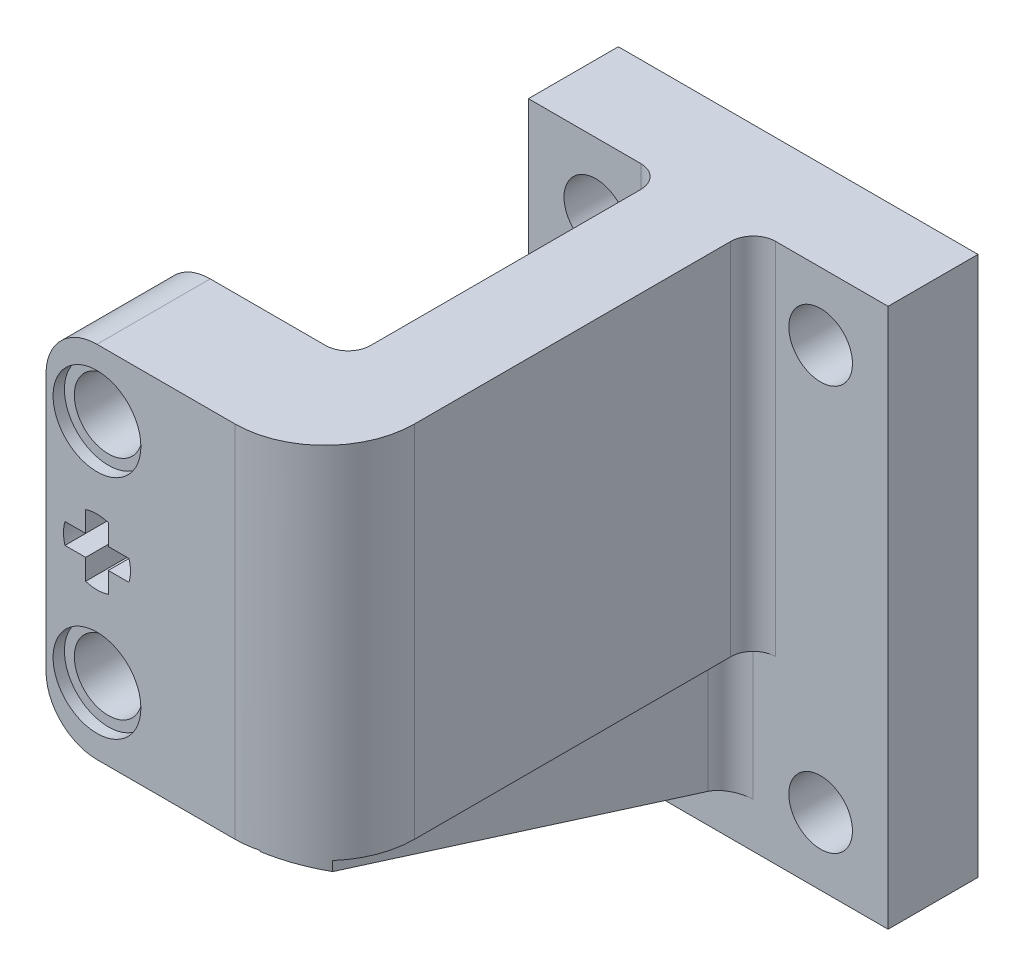
SolidWorks part; units mm, degrees
ref_plane "Front Plane" through (0, 0, 0) normal (0, 0, 1) x (1, 0, 0)
ref_plane "Top Plane" through (0, 0, 0) normal (0, 1, 0) x (1, 0, 0)
ref_plane "Right Plane" through (0, 0, 0) normal (1, 0, 0) x (0, 0, -1)
sketch "Sketch1" plane through (0, 0, 0) normal (0, 1, 0) x (1, 0, 0)
  line L0 (0, 0) -> (0, -22.2563)
  line L1 (0, -22.2563) -> (-13.335, -22.2563)
  line L2 (-13.335, -22.2563) -> (-13.335, -30.2563)
  line L3 (-13.335, -30.2563) -> (6.35, -30.2563)
  line L4 (6.35, -30.2563) -> (6.35, 0)
  line L5 (6.35, 0) -> (15.875, 0)
  line L6 (15.875, 0) -> (15.875, 6.35)
  line L7 (15.875, 6.35) -> (-9.525, 6.35)
  line L8 (-9.525, 6.35) -> (-9.525, 0)
  line L9 (-9.525, 0) -> (0, 0)
  point P3 (-13.335, -26.2563)
  point P12 (3.175, 6.35)
  dimension "D1" = 25.4
  dimension "D2" = 6.35
  dimension "D3" = 6.35
  dimension "D4" = 8
  dimension "D5" = 32.6063
  dimension "D6" = 16.51
extrude "Boss-Extrude1" add sketch "Sketch1" along normal mid plane 25.4 contours L0 L1 L2 L3 L4 L5 L6 L7 L8 L9
sketch "Sketch2" plane through (0, 0, 30.2563) normal (0, 0, 1) x (1, 0, 0)
  line L0 (-10.535, 0.7314) -> (-10.535, 2.1941)
  line L1 (-8.935, 2.1941) -> (-8.935, 0.7314)
  line L2 (-10.535, 0.7314) -> (-8.935, 0.7314) construction
  line L3 (-10.535, 0.7314) -> (-10.535, -0.7314) construction
  line L4 (-10.535, 0.7314) -> (-11.9977, 0.7314)
  line L5 (-11.9977, -0.7314) -> (-10.535, -0.7314)
  line L6 (-10.535, -0.7314) -> (-10.535, -2.1941)
  line L7 (-8.935, -2.1941) -> (-8.935, -0.7314)
  line L8 (-8.935, -0.7314) -> (-7.4723, -0.7314)
  line L9 (-8.935, 0.7314) -> (-7.4723, 0.7314)
  line L10 (-7.4723, 0.7314) -> (-9.5048, 0.7314)
  line L11 (-13.335, 12.7) -> (-13.335, -12.7) construction
  circle A0 centre (-9.735, 0) radius 2.5157 construction
  circle A1 centre (-9.735, 8) radius 3.1
  circle A2 centre (-9.735, -8) radius 3.1
  circle A3 centre (-9.735, 8) radius 2.4
  circle A4 centre (-9.735, -8) radius 2.4
  arc A5 (-10.535, 2.1941) -> (-8.935, 2.1941) centre (-9.735, -0.2798) cw
  arc A6 (-11.9977, 0.7314) -> (-11.9977, -0.7314) centre (-9.5027, 0) ccw
  arc A7 (-10.535, -2.1941) -> (-8.935, -2.1941) centre (-9.735, 0.2798) ccw
  arc A8 (-7.4723, 0.7314) -> (-7.4723, -0.7314) centre (-9.9673, 0) cw
  point P12 (-9.735, 0.7314)
  point P27 (-10.6821, 7.6255)
  point P28 (0, 0)
  point P29 (0, 0)
  point P30 (-9.0487, -2.2513)
  point P31 (0, 0)
  point P33 (0, 0)
  point P34 (-12.1027, 0)
  point P35 (-9.735, -2.3202)
  dimension "D1" = 6.2
  dimension "D2" = 4.8
  dimension "D7" = 2.6
  dimension "D3" = 8
  dimension "D4" = 8
  dimension "D5" = 1.4627
  dimension "D6" = 1.6
  dimension "D8" = 3.6
extrude "Cut-Extrude1" cut sketch "Sketch2" against normal blind 25.4 contours A8 L9 L1 A5 L0 L4 A6 L5 L6 A7 L7 L8 | A4 | A3 region at (-9.735, 0, 30.2563) region at (-9.735, -8, 30.2563)
extrude "Cut-Extrude2" cut sketch "Sketch2<3>" against normal blind 0.8 contours A1 | A2
sketch "Sketch2<3>" plane through (0, 0, 30.2563) normal (0, 0, 1) x (1, 0, 0) same geometry as "Sketch2"
ref_plane "Plane1" through (0, 0, 26.2563) normal (0, 0, 1) x (1, 0, 0)
mirror "Mirror1" about plane through (0, 0, 26.2563) normal (0, 0, 1) of "Cut-Extrude2"
fillet "Fillet1" radius 3.6 2 edges at (-13.335, -12.7, 26.2563) (-13.335, 12.7, 26.2563)
sketch "Sketch7" plane through (0, 0, -6.35) normal (0, 0, -1) x (-1, 0, 0)
  line L5 (9.525, 12.7) -> (9.525, -12.7) construction
  line L6 (-15.875, 12.7) -> (9.525, 12.7)
  line L8 (-15.875, 12.7) -> (-15.875, -25.4)
  line L9 (-15.875, -25.4) -> (9.525, -25.4)
  line L10 (9.525, 12.7) -> (9.525, -25.4)
  dimension "D1" = 38.1
extrude "Boss-Extrude2" add sketch "Sketch7" against normal up to surface (6.35 mm away) up to face at (11.1125, 0, 0)
hole_wizard "#8 Clearance Hole1" positions "Sketch5" profile "Sketch6" hole size "#8" standard "ANSI Inch" end condition up to next
sketch "Sketch5" plane through (0, 0, -6.35) normal (0, 0, -1) x (-1, 0, 0)
  line L2 (9.525, 12.7) -> (9.525, -25.4) construction
  line L5 (9.525, -25.4) -> (9.525, 12.7) construction
  line L6 (-15.875, 12.7) -> (-15.875, -25.4) construction
  line L7 (-15.875, 12.7) -> (9.525, 12.7) construction
  point P0 (-11.1125, 7.9375)
  point P2 (4.7625, 7.9375)
  point P4 (4.7625, -20.6375)
  point P6 (-11.1125, -20.6375)
  point P27 (-11.1125, 20.6375)
  point P28 (-11.1125, 8.1858)
  point P29 (0, 0)
  dimension "D1" = 4.7625
  dimension "D2" = 4.7625
  dimension "D3" = 4.7625
  dimension "D4" = 20.6375
sketch "Sketch6" plane through (11.1125, 7.9375, -6.35) normal (1, 0, 0) x (0, 1, 0)
  line L0 (0, 0) -> (0, 6.35)
  line L1 (0, 6.35) -> (2.2479, 6.35)
  line L2 (2.2479, 6.35) -> (2.2479, 0)
  line L5 (2.2479, 0) -> (0, 0)
  line L11 (0, -6.35) -> (0, 107.95) construction
  dimension "Thru Hole Dia." = 4.4958
  dimension "Thru Hole Depth" = 6.35
ref_plane "Plane2" through (3.175, 0, 0) normal (1, 0, 0) x (0, 0, -1)
sketch "Sketch8" plane through (3.175, 0, 0) normal (1, 0, 0) x (0, 0, -1)
  line L0 (0, -22.225) -> (-30.2563, -12.7)
  line L1 (0, 12.7) -> (0, -25.4) construction
  line L2 (-30.2563, -12.7) -> (0, -12.7) construction
  line L3 (-30.2563, -12.7) -> (0, -12.7)
  line L4 (0, -12.7) -> (0, -22.225)
  point P6 (-27.5683, -12.7)
  dimension "D1" = 3.175
extrude "Boss-Extrude3" add sketch "Sketch8" along normal mid plane 3.175 contours L0 L3 L4
fillet "Fillet2" radius 6.35 1 edges at (6.35, 0, 30.2563)
fillet "Fillet3" radius 1.5875 1 edges at (0, 0, 22.2563)
fillet "Fillet4" radius 1.5875 4 edges at (0, 0, 0) (6.35, 0, 0) (1.5875, -17.4625, 0) (4.7625, -17.4625, 0)
